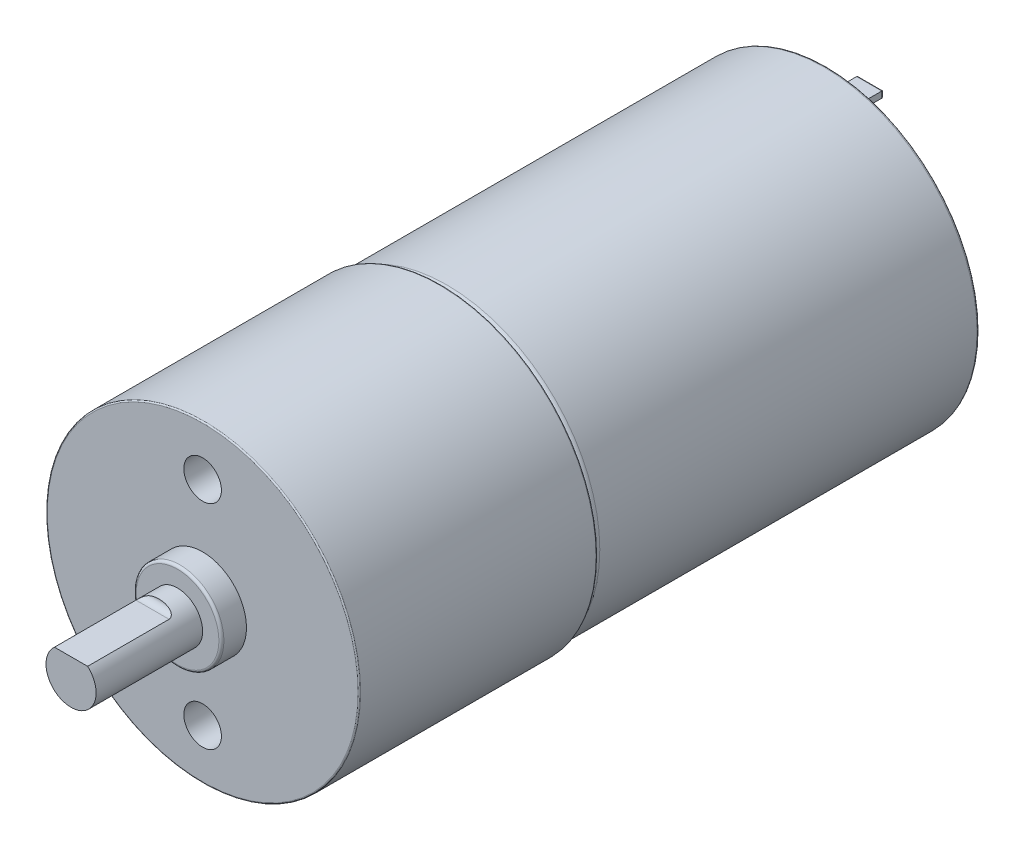
SolidWorks part; units mm, degrees
ref_plane "Ön Düzlem" through (0, 0, 0) normal (0, 0, 1) x (1, 0, 0)
ref_plane "Üst Düzlem" through (0, 0, 0) normal (0, 1, 0) x (1, 0, 0)
ref_plane "Sağ Düzlem" through (0, 0, 0) normal (1, 0, 0) x (0, 0, -1)
sketch "Çizim2" plane through (0, 0, 0) normal (0, 0, 1) x (1, 0, 0)
  circle A0 centre (0, 0) radius 12.2
  dimension "D1" = 24.4
extrude "Yükseklik-Ekstrüzyon1" add sketch "Çizim2" along normal blind 30.8
fillet "Radyus1" radius 0.5 1 edges at (12.2, 0, 30.8)
sketch "Çizim3" plane through (0, 0, 30.8) normal (0, 0, 1) x (1, 0, 0)
  circle A0 centre (0, 0) radius 12.5
  dimension "D1" = 25
extrude "Yükseklik-Ekstrüzyon2" add sketch "Çizim3" along normal blind 19
sketch "Çizim4" plane through (0, 0, 49.8) normal (0, 0, 1) x (1, 0, 0)
  circle A0 centre (0, 0) radius 3.5
  dimension "D1" = 7
extrude "Yükseklik-Ekstrüzyon3" add sketch "Çizim4" along normal blind 2
sketch "Çizim5" plane through (0, 0, 0) normal (0, 0, -1) x (-1, 0, 0)
  circle A0 centre (0, 0) radius 3.225
  dimension "D1" = 6.45
extrude "Yükseklik-Ekstrüzyon4" add sketch "Çizim5" along normal blind 1.7
sketch "Çizim6" plane through (0, 0, 51.8) normal (0, 0, 1) x (1, 0, 0)
  circle A0 centre (0, 0) radius 2
  dimension "D1" = 4
extrude "Yükseklik-Ekstrüzyon5" add sketch "Çizim6" along normal blind 8.5
sketch "Çizim7" plane through (0, 0, 60.3) normal (0, 0, 1) x (1, 0, 0)
  line L0 (-1.3229, 1.5) -> (1.3229, 1.5)
  arc A0 (1.3229, 1.5) -> (-1.3229, 1.5) centre (0, 0) ccw
extrude "Kes-Ekstrüzyon1" cut sketch "Çizim7" against normal blind 7
fillet "Radyus2" radius 0.5 1 edges at (0, 1.5, 53.3)
fillet "Radyus3" radius 0.2 1 edges at (3.5, 0, 51.8)
fillet "Radyus4" radius 0.3 1 edges at (-3.225, 0, -1.7)
fillet "Radyus5" radius 0.2 1 edges at (12.2, 0, 0)
fillet "Radyus6" radius 0.1 1 edges at (12.5, 0, 30.8)
fillet "Radyus7" radius 0.1 1 edges at (12.5, 0, 49.8)
sketch "Çizim8" plane through (0, 0, 49.8) normal (0, 0, 1) x (1, 0, 0)
  line L0 (0, 13.1703) -> (0, 10)
  circle A0 centre (0, 8.5) radius 1.5
  circle A1 centre (0, -8.5) radius 1.5
  dimension "D1" = 3
  dimension "D2" = 3
  dimension "D3" = 8.5
  dimension "D4" = 8.5
extrude "Kes-Ekstrüzyon2" cut sketch "Çizim8" against normal blind 3.5 contours A0 | A1 region at (0, 8.5, 49.8) region at (0, -8.5, 49.8)
sketch "Çizim9" plane through (0, 0, 0) normal (0, 0, -1) x (-1, 0, 0)
  line L3 (1, 8.75) -> (-1, 8.75)
  line L4 (1, 8.75) -> (1, 9.25)
  line L5 (1, 9.25) -> (-1, 9.25)
  line L6 (-1, 8.75) -> (-1, 9.25)
  line L9 (1, -9.25) -> (-1, -9.25)
  line L10 (1, -9.25) -> (1, -8.75)
  line L11 (1, -8.75) -> (-1, -8.75)
  line L12 (-1, -9.25) -> (-1, -8.75)
  point P4 (0, 9)
  point P10 (0, -9)
  dimension "D1" = 0.5
  dimension "D2" = 0.5
  dimension "D3" = 2
  dimension "D4" = 2
extrude "Yükseklik-Ekstrüzyon8" add sketch "Çizim9" along normal blind 3.5
fillet "Radyus8" radius 0.1 8 edges at (0, 8.75, -3.5) (0, 9.25, -3.5) (-1, 9, -3.5) (1, 9, -3.5) (0, -9.25, -3.5) (0, -8.75, -3.5) (-1, -9, -3.5) (1, -9, -3.5)
